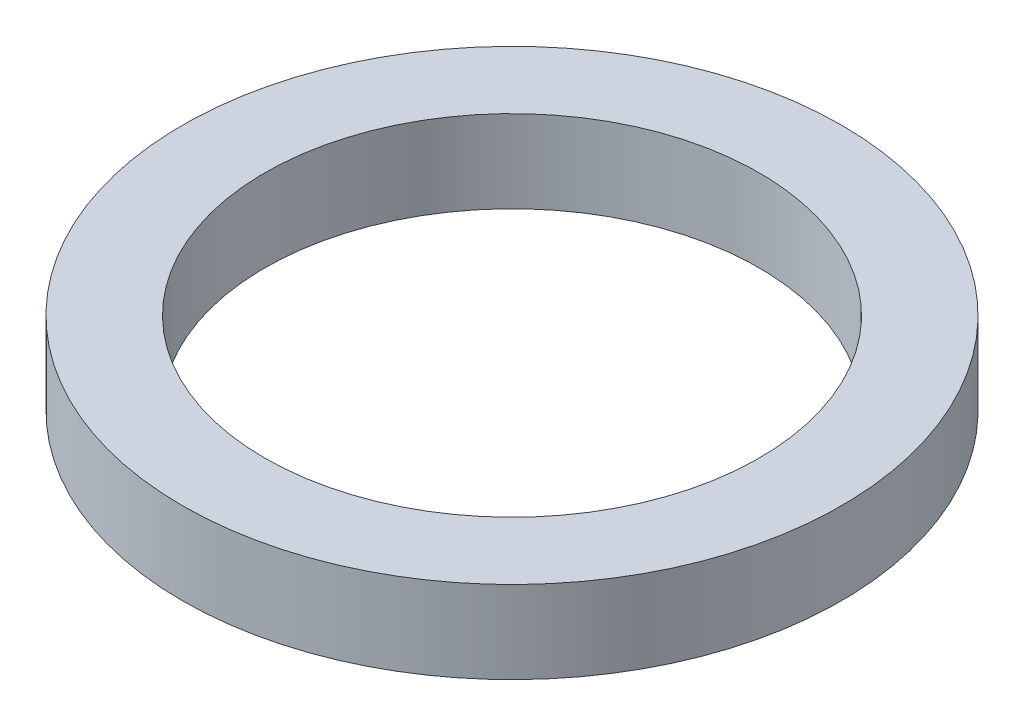
SolidWorks part; units mm, degrees
ref_plane "Front Plane" through (0, 0, 0) normal (0, 0, 1) x (1, 0, 0)
ref_plane "Top Plane" through (0, 0, 0) normal (0, 1, 0) x (1, 0, 0)
ref_plane "Right Plane" through (0, 0, 0) normal (1, 0, 0) x (0, 0, -1)
sketch "Sketch1" plane through (0, 0, 0) normal (0, 1, 0) x (1, 0, 0)
  circle A0 centre (0, 0) radius 4
  circle A1 centre (0, 0) radius 3
  dimension "D1" = 8
  dimension "D2" = 6
extrude "Boss-Extrude1" add sketch "Sketch1" along normal blind 1
equation "\"N_pin\"= 24"
equation "\"R_pin\"= 60"
equation "\"d_pin\"= 13"
equation "\"e\"= 1.5"
equation "\"t_disk\"= 5"
equation "\"N_outpin\"= 8"
equation "\"R_outpin\"= 34"
equation "\"d_outpin\"= 13"
equation "\"N_lobes\"= \"N_pin\" - 1"
equation "\"d_outhole\"= \"d_outpin\" + 2 * \"e\""
equation "\"ratio\"= \"N_lobes\""
equation "\"d_center\"= 24"
equation "\"a_hole1\"= 0 / \"N_lobes\""
equation "\"a_hole2\"= 360 / \"N_disk\" / \"N_lobes\""
equation "\"a_hole3\"= 720 / \"N_disk\" / \"N_lobes\""
equation "\"N_disk\"= 3"
equation "\"t_gap\"= 0.5"
equation "\"L_stack\"= \"N_disk\" * \"t_disk\" + (\"N_disk\" - 1) * \"t_gap\""
equation "\"d_pinshaft\"= 6"
equation "\"d_ecc\"= 15"
equation "\"d_outbrg\"= 47"
equation "\"w_outbrg\"= 7"
equation "\"d_outshaft\"= 35"
equation "\"w_brg\"= 5"
equation "\"c_run\"= 0.5"
equation "\"c_ax\"= 0.3"
equation "\"D_pocket\"= 2 * \"R_pin\" + \"d_pin\" + 2 * \"c_run\""
equation "\"h_pocket\"= \"L_stack\" + 2 * \"c_ax\""
equation "\"t_floor\"= 8"
equation "\"d_insert\"= 5.6"
equation "\"N_bolt\"= 8"
equation "\"R_bolt\"= \"D_pocket\" / 2 + 2 + \"d_insert\" / 2"
equation "\"D_housing\"= 2 * (\"R_bolt\" + \"d_insert\" / 2 + 2.5)"
equation "\"D1@Sketch1\"=\"d_pinshaft\"+2"
equation "\"D2@Sketch1\"=\"d_pinshaft\""
equation "\"D1@Boss-Extrude1\"=1"
